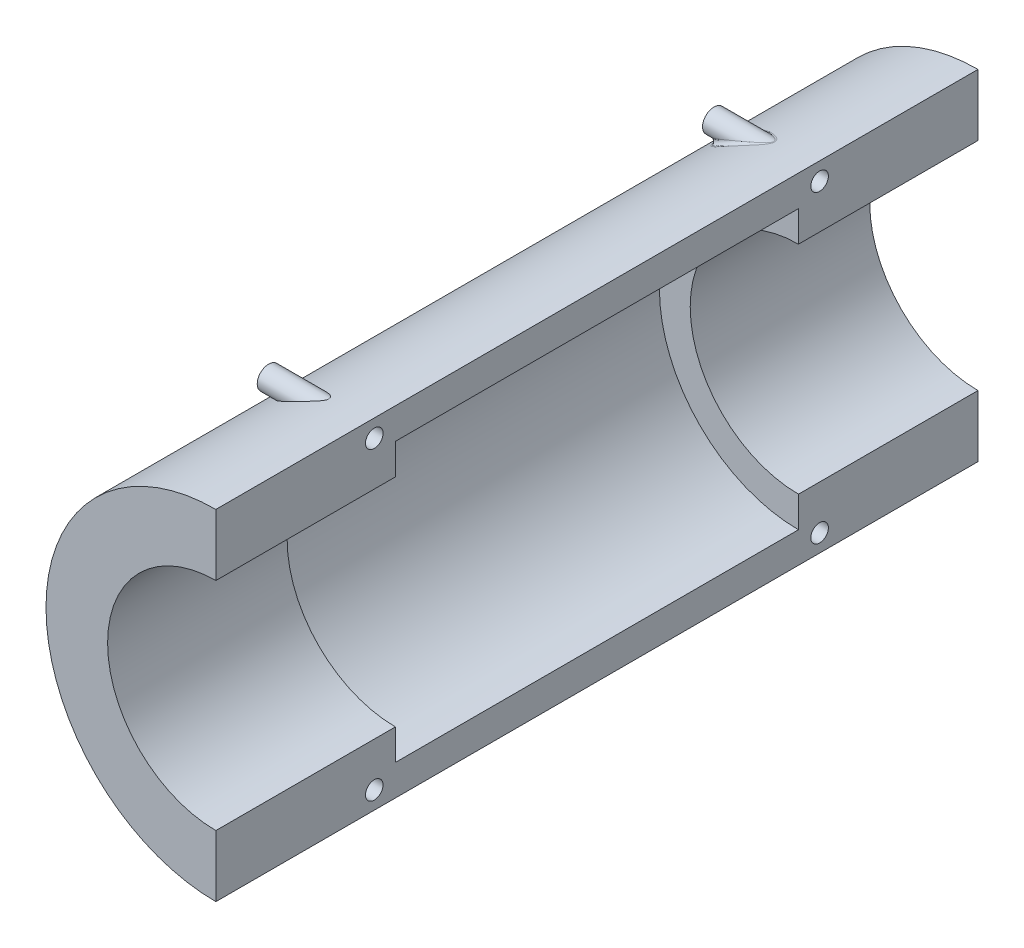
SolidWorks part; units mm, degrees
ref_plane "Front Plane" through (0, 0, 0) normal (0, 0, 1) x (1, 0, 0)
ref_plane "Top Plane" through (0, 0, 0) normal (0, 1, 0) x (1, 0, 0)
ref_plane "Right Plane" through (0, 0, 0) normal (1, 0, 0) x (0, 0, -1)
sketch "Sketch1" plane through (0, 0, 0) normal (0, 0, 1) x (1, 0, 0)
  line L0 (0, 15.621) -> (0, -15.621) construction
  line L1 (0, 24.511) -> (0, 15.621)
  line L2 (0, -24.511) -> (0, -15.621)
  arc A0 (0, 15.621) -> (0, -15.621) centre (0, 0) ccw
  arc A1 (0, 24.511) -> (0, -24.511) centre (0, 0) ccw
  dimension "D1" = 31.242
  dimension "D2" = 8.89
extrude "Boss-Extrude1" add sketch "Sketch1" along normal blind 25.908
sketch "Sketch2" plane through (0, 0, 25.908) normal (0, 0, 1) x (1, 0, 0)
  line L0 (0, 20.066) -> (0, -20.066) construction
  line L1 (0, 24.511) -> (0, 20.066)
  line L2 (0, -24.511) -> (0, -20.066)
  arc A0 (0, 20.066) -> (0, -20.066) centre (0, 0) ccw
  arc A1 (0, 24.511) -> (0, -24.511) centre (0, 0) ccw
  dimension "D1" = 40.132
  dimension "D2" = 4.445
extrude "Boss-Extrude2" add sketch "Sketch2" along normal blind 29.083
sketch "Sketch3" plane through (0, 0, 0) normal (1, 0, 0) x (0, 0, -1)
  line L0 (-54.991, 24.511) -> (0, 24.511) construction
  line L1 (0, 15.621) -> (0, 24.511) construction
  line L2 (0, 0) -> (-66.0113, 0) construction
  circle A0 centre (-22.86, 21.971) radius 1.27
  circle A1 centre (-22.86, -21.971) radius 1.27
  dimension "D1" = 2.54
  dimension "D2" = 2.54
  dimension "D3" = 22.86
extrude "Cut-Extrude1" cut sketch "Sketch3" against normal blind 38.1
sketch "Sketch4" plane through (0, 0, 0) normal (1, 0, 0) x (0, 0, -1)
  circle A0 centre (-22.86, 21.971) radius 1.27
  circle A1 centre (-22.86, 21.971) radius 1.651
  dimension "D1" = 2.54
  dimension "D2" = 0.381
ref_plane "Plane1" through (0, 0, 54.991) normal (0, 0, 1) x (1, 0, 0)
mirror "Mirror3" about plane through (0, 0, 54.991) normal (0, 0, 1) of "Boss-Extrude2"
mirror "Mirror4" about plane through (0, 0, 54.991) normal (0, 0, 1) of "Boss-Extrude1"
mirror "Mirror5" about plane through (0, 0, 54.991) normal (0, 0, 1) of "Cut-Extrude1"
extrude "Boss-Extrude5" add sketch "Sketch4" against normal blind 15.24
fillet "Fillet2" radius 0.508 1 edges at (-13.6932, 20.3294, 22.6841)
mirror "Mirror8" about plane through (0, 0, 0) normal (0, 1, 0) of "Boss-Extrude5"
mirror "Mirror9" about plane through (0, 0, 54.991) normal (0, 0, 1) of "Mirror8"
